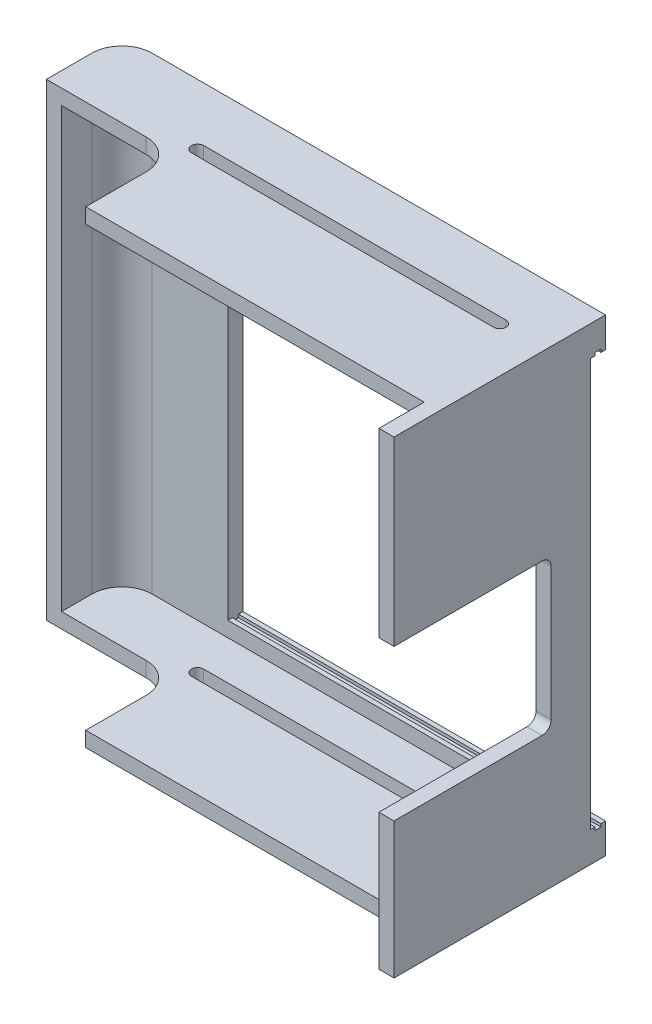
SolidWorks part; units mm, degrees
ref_plane "Front Plane" through (0, 0, 0) normal (0, 0, 1) x (1, 0, 0)
ref_plane "Top Plane" through (0, 0, 0) normal (0, 1, 0) x (1, 0, 0)
ref_plane "Right Plane" through (0, 0, 0) normal (1, 0, 0) x (0, 0, -1)
sketch "Sketch1" plane through (0, 0, 0) normal (0, 1, 0) x (1, 0, 0)
  line L1 (-86.5373, 36.1567) -> (63.4627, 36.1567)
  line L2 (-86.5373, 36.1567) -> (-86.5373, -18.8433)
  line L3 (-86.5373, -18.8433) -> (63.4627, -18.8433)
  line L4 (63.4627, 36.1567) -> (63.4627, -18.8433)
  line L5 (-86.5373, 11.1567) -> (-48.5373, 11.1567)
  line L6 (-86.5373, 11.1567) -> (-86.5373, -18.8433)
  line L7 (-86.5373, -18.8433) -> (-48.5373, -18.8433)
  line L8 (-48.5373, 11.1567) -> (-48.5373, -18.8433)
  dimension "D1" = 55
  dimension "D2" = 150
  dimension "D3" = 25
  dimension "D4" = 38
extrude "Boss-Extrude1" add sketch "Sketch1" along normal blind 5 contours L5 L8 L3 L4 L1 L2 region at (-2.5584, 0, -10.6609)
sketch "Sketch2" plane through (0, 5, 0) normal (0, 1, 0) x (1, 0, 0)
  line L0 (63.4627, 36.1567) -> (63.4627, -18.8433) construction
  line L1 (-86.5373, 36.1567) -> (63.4627, 36.1567)
  line L2 (-86.5373, 36.1567) -> (-86.5373, 31.1567)
  line L3 (-86.5373, 31.1567) -> (63.4627, 31.1567)
  line L4 (63.4627, 36.1567) -> (63.4627, 31.1567)
  dimension "D1" = 5
extrude "Boss-Extrude2" add sketch "Sketch2" along normal blind 145
sketch "Sketch4" plane through (0, 0, -31.1567) normal (0, 0, 1) x (1, 0, 0)
  line L0 (63.4627, 77.5) -> (-86.5373, 77.5) construction
  line L1 (63.4627, 150) -> (63.4627, 5) construction
  line L2 (-86.5373, 150) -> (-86.5373, 5) construction
ref_plane "Plane1" through (0, 77.5, 0) normal (0, 1, 0) x (-1, 0, 0)
mirror "Mirror1" about plane through (0, 77.5, 0) normal (0, 1, 0) of "Boss-Extrude1"
ref_plane "Plane2" through (63.4627, 150, -31.1567) normal (0, -1, 0) x (-1, 0, 0)
sketch "Sketch6" plane through (63.4627, 0, 0) normal (1, 0, 0) x (0, 0, -1)
  line L1 (36.1567, 155) -> (-33.8433, 155)
  line L2 (36.1567, 155) -> (36.1567, 0)
  line L3 (36.1567, 0) -> (-33.8433, 0)
  line L4 (-33.8433, 155) -> (-33.8433, 0)
  line L5 (36.1567, 0) -> (-18.8433, 0) construction
  dimension "D1" = 70
extrude "Boss-Extrude3" add sketch "Sketch6" along normal blind 5
sketch "Sketch7" plane through (68.4627, 0, 0) normal (1, 0, 0) x (0, 0, -1)
  line L0 (-33.8433, 155) -> (-33.8433, 0) construction
  line L1 (-33.8433, 95) -> (18.1567, 95)
  line L2 (-33.8433, 95) -> (-33.8433, 45)
  line L3 (-33.8433, 45) -> (18.1567, 45)
  line L4 (18.1567, 95) -> (18.1567, 45)
  line L6 (36.1567, 0) -> (36.1567, 155) construction
  line L7 (-33.8433, 0) -> (36.1567, 0) construction
  dimension "D1" = 50
  dimension "D2" = 45
  dimension "D3" = 18
extrude "Cut-Extrude1" cut sketch "Sketch7" against normal blind 5
sketch "Sketch8" plane through (-86.5373, 0, 0) normal (-1, 0, 0) x (0, 0, 1)
  line L1 (-36.1567, 0) -> (-11.1567, 0)
  line L2 (-36.1567, 0) -> (-36.1567, 155)
  line L3 (-36.1567, 155) -> (-11.1567, 155)
  line L4 (-11.1567, 0) -> (-11.1567, 155)
extrude "Boss-Extrude4" add sketch "Sketch8" along normal blind 5
fillet "Fillet1" radius 10 3 edges at (-91.5373, 77.5, -36.1567) (-48.5373, 152.5, -11.1567) (-48.5373, 2.5, -11.1567)
fillet "Fillet2" radius 10 1 edges at (-86.5373, 77.5, -31.1567)
sketch "Sketch9" plane through (68.4627, 0, 0) normal (1, 0, 0) x (0, 0, -1)
  line L0 (36.1567, 0) -> (36.1567, 155) construction
  line L1 (36.1567, 145) -> (31.1567, 145)
  line L2 (36.1567, 145) -> (36.1567, 10)
  line L3 (36.1567, 10) -> (31.1567, 10)
  line L4 (31.1567, 145) -> (31.1567, 10)
  line L5 (36.1567, 155) -> (-33.8433, 155) construction
  line L6 (-33.8433, 0) -> (36.1567, 0) construction
  line L7 (81.95, 77.5) -> (-81.95, 77.5) construction
  line L8 (34.6567, 145) -> (32.6567, 145)
  line L9 (34.6567, 145) -> (34.6567, 146)
  line L10 (34.6567, 146) -> (32.6567, 146)
  line L11 (32.6567, 145) -> (32.6567, 146)
  line L12 (34.6567, 9) -> (32.6567, 9)
  line L13 (32.6567, 10) -> (32.6567, 9)
  line L14 (34.6567, 10) -> (32.6567, 10)
  line L15 (34.6567, 10) -> (34.6567, 9)
  line M15 (36.1567, 0) -> (36.1567, 155)
  dimension "D1" = 5
  dimension "D2" = 10
  dimension "D3" = 10
  dimension "D4" = 2
  dimension "D5" = 1.5
  dimension "D6" = 1
extrude "Cut-Extrude2" cut sketch "Sketch9" against normal blind 120 contours L1 L4 L3 M15 | L15 L3 L13 L12 | L11 L1 L9 L10 region at (68.4627, 77.5, -33.6567) region at (68.4627, 145.5, -33.6567) region at (68.4627, 9.5, -33.6567)
fillet "Fillet5" radius 3 2 edges at (65.9627, 45, -18.1567) (65.9627, 95, -18.1567)
sketch "Sketch11" plane through (0, 0, 0) normal (0, -1, 0) x (1, 0, 0)
  line L0 (53.4627, -16.1567) -> (-46.5373, -16.1567) construction
  line L1 (53.4627, -18.2067) -> (-46.5373, -18.2067)
  line L2 (53.4627, -14.1067) -> (-46.5373, -14.1067)
  line L3 (68.4627, 33.8433) -> (68.4627, -36.1567) construction
  line L4 (-81.5373, -36.1567) -> (68.4627, -36.1567) construction
  arc A0 (53.4627, -18.2067) -> (53.4627, -14.1067) centre (53.4627, -16.1567) ccw
  arc A1 (-46.5373, -14.1067) -> (-46.5373, -18.2067) centre (-46.5373, -16.1567) ccw
  point P2 (3.4627, -16.1567)
  dimension "D1" = 4.1
  dimension "D2" = 100
  dimension "D3" = 65
  dimension "D4" = 20
extrude "Cut-Extrude4" cut sketch "Sketch11" against normal up to surface (155 mm away) up to face at (-15.6373, 155, -2.0709)
